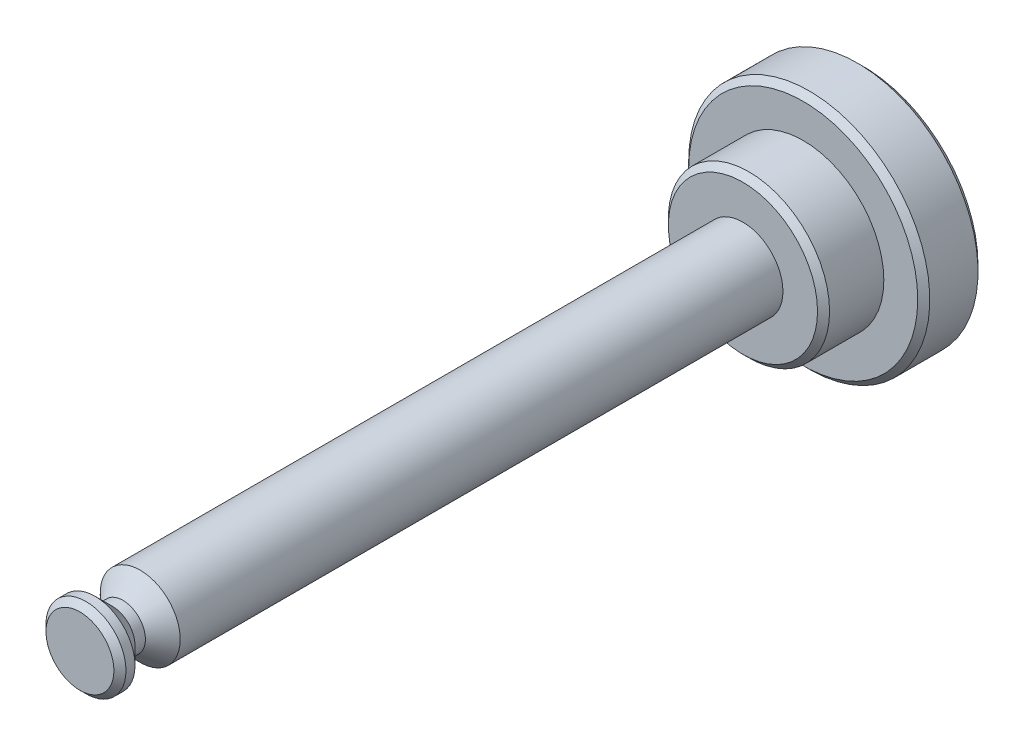
SolidWorks part; units mm, degrees
ref_plane "Front" through (0, 0, 0) normal (0, 0, 1) x (1, 0, 0)
ref_plane "Top" through (0, 0, 0) normal (0, 1, 0) x (1, 0, 0)
ref_plane "Right" through (0, 0, 0) normal (1, 0, 0) x (0, 0, -1)
sketch "Sketch1" plane through (0, 0, 0) normal (0, 0, 1) x (1, 0, 0)
  circle A0 centre (0, 0) radius 2.675
  dimension "D1" = 5.35
extrude "Countersink" add sketch "Sketch1" against normal blind 2
sketch "Sketch2" plane through (0, 0, 0) normal (0, 0, 1) x (1, 0, 0)
  circle A0 centre (0, 0) radius 1.3272
extrude "Shaft" add sketch "Sketch2" along normal blind 22
sketch "Sketch3" plane through (0, 0, -2) normal (0, 0, -1) x (-1, 0, 0)
  circle A3 centre (0, 0) radius 4
  point P0 (0, 0)
  dimension "D1" = 8
extrude "Boss-Extrude3" add sketch "Sketch3" along normal blind 2
sketch "Sketch4" plane through (0, 0, 0) normal (1, 0, 0) x (0, 0, -1)
  line L0 (0, 0) -> (-20.75, 0) construction
  line L1 (-20.75, 0) -> (-20.75, 4.3666) construction
  line L2 (-21.5, 1.3272) -> (-20, 1.3272)
  line L3 (0, 1.3272) -> (-22, 1.3272) construction
  line L6 (-20, 1.3272) -> (-20.5772, 0.75)
  line L7 (-20.5772, 0.75) -> (-20.9228, 0.75)
  line L8 (-20.9228, 0.75) -> (-21.5, 1.3272)
  point P8 (-20.2229, 0.8874)
  point P10 (-20.2057, 0.9448)
  point P12 (-21.2512, 1.3272)
  point P13 (-20.5, 4.3666)
  dimension "D1" = 20.75
  dimension "D2" = 1.5
  dimension "D3" = 45
  dimension "D4" = 1.5
revolve "e-Clip Notch" cut sketch "Sketch4" angle 360 about L0
chamfer "Deburs" distance 0.2 angle 45 4 edges at (1.3272, 0, 22) (-4, 0, -2) (-4, 0, -4) (2.675, 0, 0)
equation "\"D1@Sketch1\"=\"Hardware Head Countersink Diameter@Box Assy.Assembly\"-.25mm"
equation "\"D1@Shaft\"=\"Hardware Length@Box Assy.Assembly\"+2mm"
equation "\"D1@Sketch4\"=\"Hardware Length@Box Assy.Assembly\" + .75mm"
